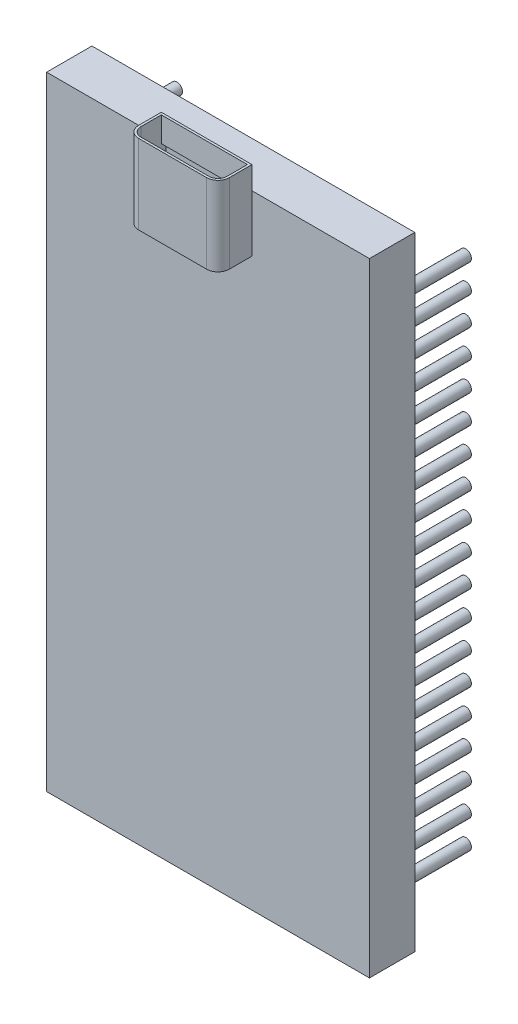
SolidWorks part; units mm, degrees
ref_plane "Front Plane" through (0, 0, 0) normal (1, 0, 0) x (0, 1, 0)
ref_plane "Top Plane" through (0, 0, 0) normal (0, 0, 1) x (0, 1, 0)
ref_plane "Right Plane" through (0, 0, 0) normal (0, 1, 0) x (-1, 0, 0)
sketch "Sketch1" plane through (0, 0, 0) normal (0, 0, 1) x (0, 1, 0)
  line L1 (-27.5, -14.25) -> (27.5, -14.25)
  line L2 (-27.5, -14.25) -> (-27.5, 14.25)
  line L3 (-27.5, 14.25) -> (27.5, 14.25)
  line L4 (27.5, -14.25) -> (27.5, 14.25)
  line L5 (-27.5, -14.25) -> (27.5, 14.25) construction
  line L6 (-27.5, 14.25) -> (27.5, -14.25) construction
  point P0 (0, 0)
  dimension "D1" = 55
  dimension "D2" = 28.5
extrude "Boss-Extrude1" add sketch "Sketch1" along normal mid plane 4
sketch "Sketch2" plane through (0, 0, 2) normal (0, 0, 1) x (1, 0, 0)
  line L0 (14.25, 27.5) -> (-14.25, 27.5) construction
  line L1 (-4.1235, 22.5) -> (3.8765, 22.5)
  line L2 (-4.1235, 22.5) -> (-4.1235, 29.5)
  line L3 (-4.1235, 29.5) -> (3.8765, 29.5)
  line L4 (3.8765, 22.5) -> (3.8765, 29.5)
  line L5 (-4.1235, 22.5) -> (3.8765, 29.5) construction
  line L6 (-4.1235, 29.5) -> (3.8765, 22.5) construction
  point P0 (-0.1235, 26)
  dimension "D1" = 7
  dimension "D2" = 8
  dimension "D3" = 2
extrude "Boss-Extrude2" add sketch "Sketch2" along normal blind 3
fillet "Fillet2" radius 1 2 edges at (-4.1235, 26, 5) (3.8765, 26, 5)
shell "Shell2" thickness 0.2 removed face at (-0.1235, 29.5, 3.7357)
sketch "Sketch3" plane through (0, 0, -2) normal (0, 0, -1) x (1, 0, 0)
  line L0 (-14.25, 27.5) -> (14.25, 27.5) construction
  line L1 (14.25, 27.5) -> (14.25, -27.5) construction
  circle A0 centre (12.75, 23) radius 0.5
  circle A1 centre (12.75, 20.5) radius 0.5
  circle A2 centre (12.75, 18) radius 0.5
  circle A3 centre (12.75, 15.5) radius 0.5
  circle A4 centre (12.75, 13) radius 0.5
  circle A5 centre (12.75, 10.5) radius 0.5
  circle A6 centre (12.75, 8) radius 0.5
  circle A7 centre (12.75, 5.5) radius 0.5
  circle A8 centre (12.75, 3) radius 0.5
  circle A9 centre (12.75, 0.5) radius 0.5
  circle A10 centre (12.75, -2) radius 0.5
  circle A11 centre (12.75, -4.5) radius 0.5
  circle A12 centre (12.75, -7) radius 0.5
  circle A13 centre (12.75, -9.5) radius 0.5
  circle A14 centre (12.75, -12) radius 0.5
  circle A15 centre (12.75, -14.5) radius 0.5
  circle A16 centre (12.75, -17) radius 0.5
  circle A17 centre (12.75, -19.5) radius 0.5
  circle A18 centre (12.75, -22) radius 0.5
  dimension "D1" = 1
  dimension "D2" = 4.5
  dimension "D3" = 1.5
  dimension "D4" = 19
extrude "Boss-Extrude3" add sketch "Sketch3" along normal blind 6
mirror "Mirror1" about plane through (0, 0, 0) normal (1, 0, 0) of "Boss-Extrude3"
